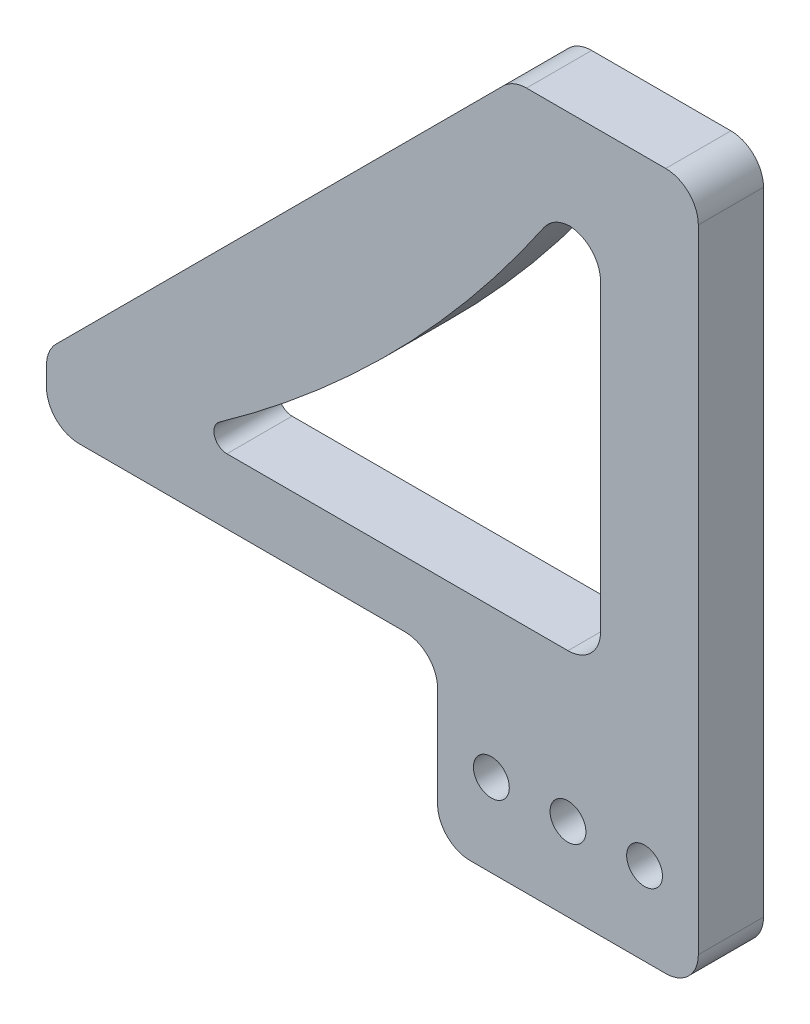
SolidWorks part; units mm, degrees
ref_plane "Front" through (0, 0, 0) normal (0, 0, 1) x (1, 0, 0)
ref_plane "Top" through (0, 0, 0) normal (0, 1, 0) x (1, 0, 0)
ref_plane "Right" through (0, 0, 0) normal (1, 0, 0) x (0, 0, -1)
sketch "Sketch1" plane through (0, 0, 0) normal (0, 0, 1) x (1, 0, 0)
  line L0 (-60, 10) -> (11.5685, 81.5685)
  line L1 (11.5685, 81.5685) -> (40, 81.5685)
  line L2 (40, 81.5685) -> (40, -25.4)
  line L3 (40, -25.4) -> (0, -25.4)
  line L4 (0, -25.4) -> (0, 0)
  line L5 (0, 0) -> (-60, 0)
  line L6 (-60, 0) -> (-60, 10)
  line L7 (-38.7868, 10) -> (17.7817, 66.5685) construction
  line L8 (17.7817, 66.5685) -> (25, 66.5685)
  line L9 (25, 66.5685) -> (25, 10)
  line L10 (25, 10) -> (-38.7868, 10)
  line L11 (-71.4288, 85.35) -> (79.9478, 85.35) construction
  line L12 (-52.5613, 0) -> (69.8542, 0) construction
  line L13 (-52.5613, 0) -> (-52.5613, -25.4) construction
  line L14 (-52.5613, -25.4) -> (69.8542, -25.4) construction
  line L15 (69.8542, 0) -> (69.8542, -25.4) construction
  circle A0 centre (8.25, -12.7) radius 2.75
  circle A1 centre (20, -12.7) radius 2.75
  circle A2 centre (31.75, -12.7) radius 2.75
  arc A3 (17.7817, 66.5685) -> (-38.7868, 10) centre (-149.0666, 176.8483) cw
  point P23 (-52.5613, -12.7)
  point P24 (0, 0)
  point P25 (20, -25.4)
  dimension "D10" = 5.5
  dimension "D11" = 5.5
  dimension "D12" = 5.5
  dimension "D14" = 200
  dimension "D1" = 15
  dimension "D2" = 15
  dimension "D3" = 15
  dimension "D4" = 10
  dimension "D5" = 80
  dimension "D6" = 25.4
  dimension "D7" = 85.35
  dimension "D8" = 40
  dimension "D9" = 45
  dimension "D13" = 100
extrude "Boss-Extrude1" add sketch "Sketch1" along normal blind 10
fillet "Fillet1" radius 5 10 edges at (17.7817, 66.5685, 5) (25, 66.5685, 5) (25, 10, 5) (0, 0, 5) (-60, 0, 5) (-60, 10, 5) (0, -25.4, 5) (40, -25.4, 5) (40, 81.5685, 5) (11.5685, 81.5685, 5)
fillet "Fillet2" radius 2 1 edges at (-38.7868, 10, 5)
